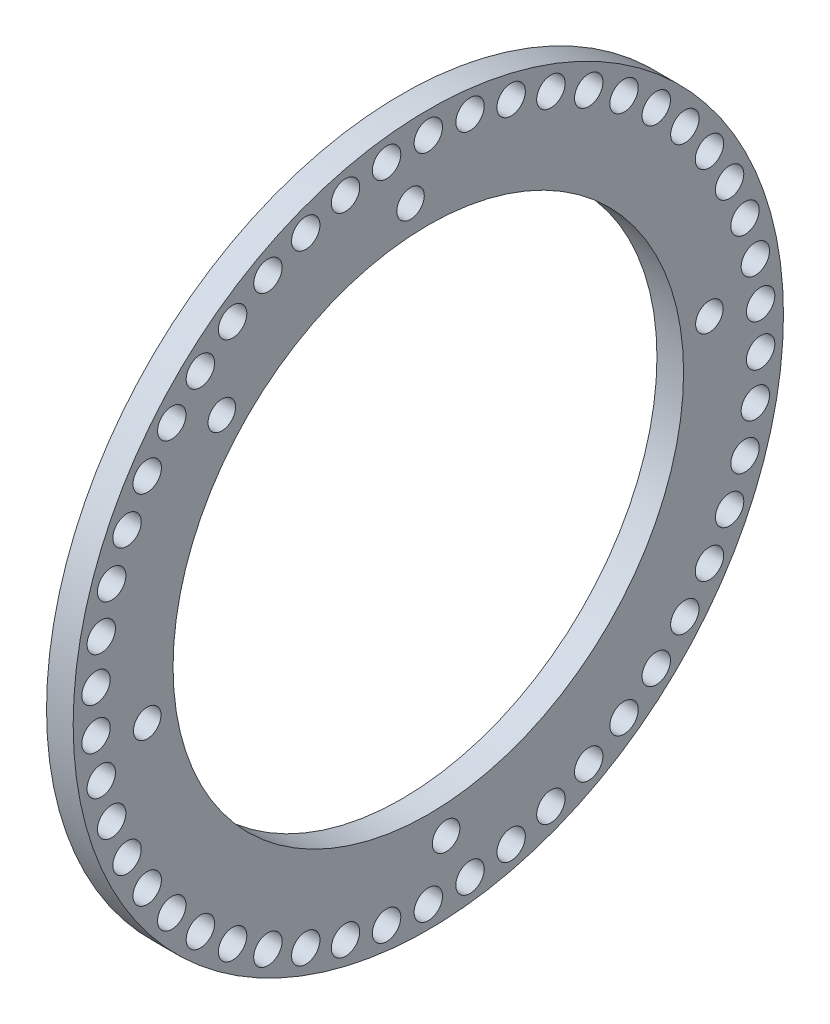
SolidWorks part; units mm, degrees
material "AISI 304"
ref_plane "Front Plane" through (0, 0, 0) normal (0, 0, 1) x (1, 0, 0)
ref_plane "Top Plane" through (0, 0, 0) normal (0, 1, 0) x (1, 0, 0)
ref_plane "Right Plane" through (0, 0, 0) normal (1, 0, 0) x (0, 0, -1)
sketch "Sketch1" plane through (0, 0, 0) normal (1, 0, 0) x (0, 0, -1)
  line L0 (0, 0) -> (0, 40) construction
  line L66 (0, 0) -> (40, 0) construction
  line L67 (0, 0) -> (-40, 0) construction
  line L72 (0, 0) -> (0, -40) construction
  circle A3 centre (0, 0) radius 40
  circle A24 centre (0, 37.5) radius 1.6
  circle A25 centre (0, 0) radius 28.75
  circle A26 centre (4.7, 37.2043) radius 1.6
  circle A27 centre (9.3259, 36.3219) radius 1.6
  circle A28 centre (13.8047, 34.8666) radius 1.6
  circle A29 centre (18.0658, 32.8615) radius 1.6
  circle A30 centre (22.0419, 30.3381) radius 1.6
  circle A31 centre (25.6705, 27.3363) radius 1.6
  circle A32 centre (28.8942, 23.9034) radius 1.6
  circle A33 centre (31.6623, 20.0935) radius 1.6
  circle A34 centre (33.931, 15.9667) radius 1.6
  circle A35 centre (35.6646, 11.5881) radius 1.6
  circle A36 centre (36.8358, 7.0268) radius 1.6
  circle A37 centre (37.426, 2.3546) radius 1.6
  circle A38 centre (37.426, -2.3546) radius 1.6
  circle A39 centre (36.8358, -7.0268) radius 1.6
  circle A40 centre (35.6646, -11.5881) radius 1.6
  circle A41 centre (33.931, -15.9667) radius 1.6
  circle A42 centre (31.6623, -20.0935) radius 1.6
  circle A43 centre (28.8942, -23.9034) radius 1.6
  circle A44 centre (25.6705, -27.3363) radius 1.6
  circle A45 centre (22.0419, -30.3381) radius 1.6
  circle A46 centre (18.0658, -32.8615) radius 1.6
  circle A47 centre (13.8047, -34.8666) radius 1.6
  circle A48 centre (9.3259, -36.3219) radius 1.6
  circle A49 centre (4.7, -37.2043) radius 1.6
  circle A50 centre (0, -37.5) radius 1.6
  circle A51 centre (-4.7, -37.2043) radius 1.6
  circle A52 centre (-9.3259, -36.3219) radius 1.6
  circle A53 centre (-13.8047, -34.8666) radius 1.6
  circle A54 centre (-18.0658, -32.8615) radius 1.6
  circle A55 centre (-22.0419, -30.3381) radius 1.6
  circle A56 centre (-25.6705, -27.3363) radius 1.6
  circle A57 centre (-28.8942, -23.9034) radius 1.6
  circle A58 centre (-31.6623, -20.0935) radius 1.6
  circle A59 centre (-33.931, -15.9667) radius 1.6
  circle A60 centre (-35.6646, -11.5881) radius 1.6
  circle A61 centre (-36.8358, -7.0268) radius 1.6
  circle A62 centre (-37.426, -2.3546) radius 1.6
  circle A63 centre (-37.426, 2.3546) radius 1.6
  circle A64 centre (-36.8358, 7.0268) radius 1.6
  circle A65 centre (-35.6646, 11.5881) radius 1.6
  circle A66 centre (-33.931, 15.9667) radius 1.6
  circle A67 centre (-31.6623, 20.0935) radius 1.6
  circle A68 centre (-28.8942, 23.9034) radius 1.6
  circle A69 centre (-25.6705, 27.3363) radius 1.6
  circle A70 centre (-22.0419, 30.3381) radius 1.6
  circle A71 centre (-18.0658, 32.8615) radius 1.6
  circle A72 centre (-13.8047, 34.8666) radius 1.6
  circle A73 centre (-9.3259, 36.3219) radius 1.6
  circle A74 centre (-4.7, 37.2043) radius 1.6
  circle A75 centre (-2.0035, 31.8444) radius 1.55
  circle A76 centre (-31.6557, -3.999) radius 1.55
  circle A77 centre (2.0035, -31.8444) radius 1.55
  circle A78 centre (31.6557, 3.999) radius 1.55
  circle A79 centre (-23.2594, 21.8421) radius 1.55
  point P9 (0, -20)
  point P11 (-20, 0)
  point P29 (20, 0)
  point P75 (0, 0)
  point P93 (0, 0)
  point P95 (0, 0)
  point P117 (0, 0)
  dimension "D1" = 50
  dimension "D2" = 80
  dimension "D3" = 57.5
  dimension "D5" = 2.5
  dimension "D10" = 6
  dimension "D4" = 3.2
  dimension "D14" = 3.1
  dimension "D15" = 3.1
  dimension "D16" = 3.1
  dimension "D17" = 3.1
  dimension "D18" = 3.1
  dimension "D6" = 6
  dimension "D7" = 6
  dimension "D8" = 6
  dimension "D9" = 6
  dimension "D12" = 6
  dimension "D13" = 6
  dimension "D11" = 6
  dimension "D19" = 6
  dimension "D20" = 6
extrude "Boss-Extrude4" add sketch "Sketch1" along normal blind 3
